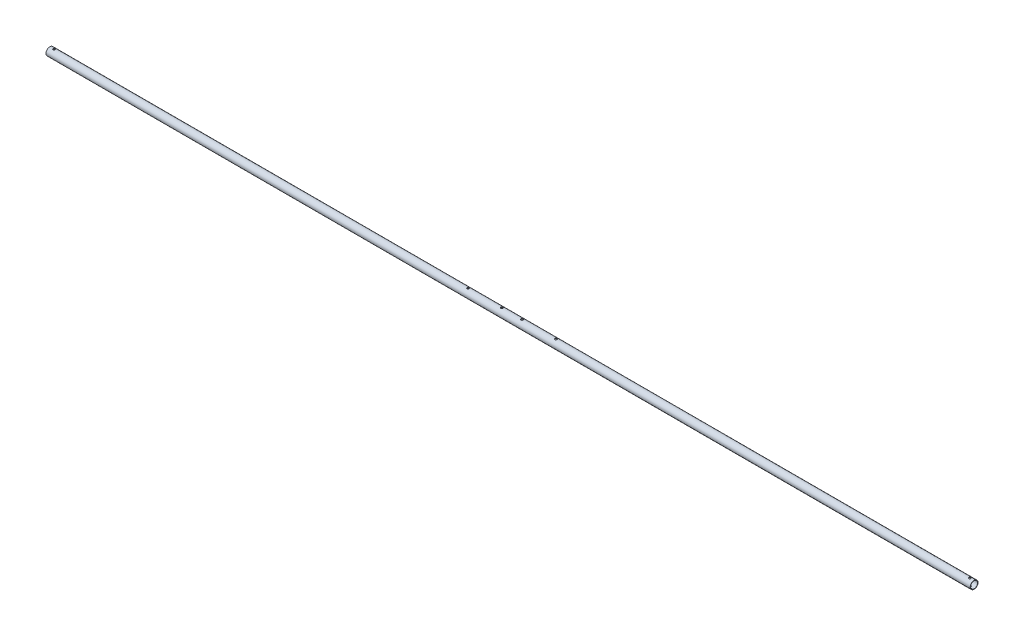
SolidWorks part; units mm, degrees
material "Galvanized Steel"
ref_plane "Front Plane" through (0, 0, 0) normal (0, 0, 1) x (1, 0, 0)
ref_plane "Top Plane" through (0, 0, 0) normal (0, 1, 0) x (1, 0, 0)
ref_plane "Right Plane" through (0, 0, 0) normal (1, 0, 0) x (0, 0, -1)
sketch "Sketch3" plane through (0, 0, 0) normal (1, 0, 0) x (0, 0, -1)
  circle A0 centre (0, 0) radius 10.4648
  circle A1 centre (0, 0) radius 11.7094
  dimension "D1" = 20.9296
  dimension "D2" = 23.4188
extrude "Boss-Extrude1" add sketch "Sketch3" along normal blind 2781.3
sketch "Sketch4" plane through (0, 0, 0) normal (0, 1, 0) x (1, 0, 0)
  circle A0 centre (1360.17, 0) radius 3.175
  circle A1 centre (1421.13, 0) radius 3.175
  circle A2 centre (1522.8316, 0) radius 3.175
  circle A3 centre (1258.4684, 0) radius 3.175
  point P0 (1390.65, 0)
  point P1 (1421.13, 0)
  point P3 (1360.17, 0)
  dimension "D4" = 6.35
  dimension "D5" = 6.35
  dimension "D6" = 132.1816
  dimension "D1" = 1390.65
  dimension "D2" = 30.48
  dimension "D3" = 30.48
  dimension "D7" = 132.1816
extrude "Cut-Extrude1" cut sketch "Sketch4" against normal through all and the other way through all
sketch "Sketch5" plane through (0, 0, 0) normal (0, 1, 0) x (1, 0, 0)
  line L0 (2781.3, -11.7094) -> (2781.3, 11.7094) construction
  circle A0 centre (12.7, 0) radius 3.175
  circle A1 centre (2768.6, 0) radius 3.175
  point P0 (12.7, 0)
  point P4 (2768.6, 0)
  dimension "D2" = 6.35
  dimension "D4" = 6.35
  dimension "D1" = 12.7
  dimension "D3" = 12.7
extrude "Cut-Extrude2" cut sketch "Sketch5" against normal through all and the other way through all
